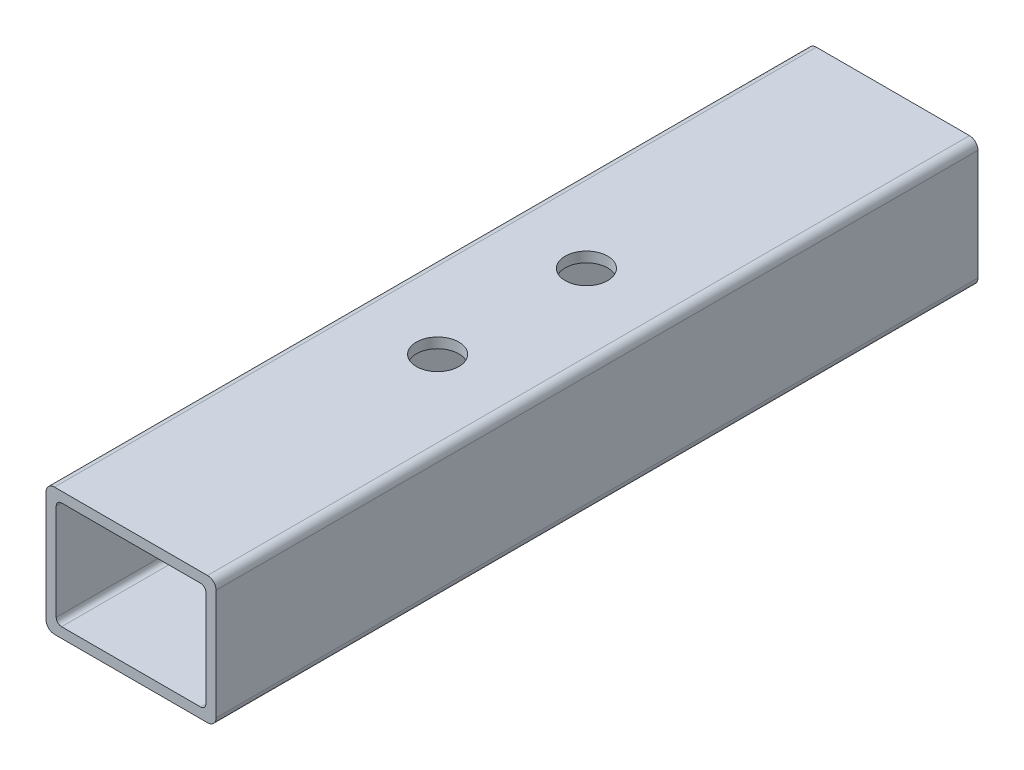
SolidWorks part; units mm, degrees
material "Plain Carbon Steel"
ref_plane "Front" through (0, 0, 0) normal (0, 0, 1) x (1, 0, 0)
ref_plane "Top" through (0, 0, 0) normal (0, 1, 0) x (1, 0, 0)
ref_plane "Right" through (0, 0, 0) normal (1, 0, 0) x (0, 0, -1)
sketch "Sketch1" plane through (0, 0, 0) normal (0, 0, 1) x (1, 0, 0)
  line L0 (-22.352, 0) -> (-25.4, 0) construction
  line L1 (22.86, -19.05) -> (-22.86, -19.05)
  line L2 (25.4, -16.51) -> (25.4, 16.51)
  line L3 (22.86, 19.05) -> (-22.86, 19.05)
  line L4 (-25.4, -16.51) -> (-25.4, 16.51)
  line L5 (25.4, -19.05) -> (-25.4, 19.05) construction
  line L6 (25.4, 19.05) -> (-25.4, -19.05) construction
  line L7 (20.7518, 16.002) -> (-20.7518, 16.002)
  line L8 (22.352, 14.4018) -> (22.352, -14.4018)
  line L9 (20.7518, -16.002) -> (-20.7518, -16.002)
  line L10 (-22.352, 14.4018) -> (-22.352, -14.4018)
  line L11 (22.352, 16.002) -> (-22.352, -16.002) construction
  line L12 (22.352, -16.002) -> (-22.352, 16.002) construction
  line L13 (0, -16.002) -> (0, -19.05) construction
  line L14 (22.352, -14.4018) -> (22.352, -19.05) construction
  line L16 (22.352, -19.05) -> (25.4, -19.05) construction
  arc A0 (-20.7518, -16.002) -> (-22.352, -14.4018) centre (-20.7518, -14.4018) cw
  arc A1 (22.352, -14.4018) -> (20.7518, -16.002) centre (20.7518, -14.4018) cw
  arc A2 (20.7518, 16.002) -> (22.352, 14.4018) centre (20.7518, 14.4018) cw
  arc A3 (-20.7518, 16.002) -> (-22.352, 14.4018) centre (-20.7518, 14.4018) ccw
  arc A4 (22.86, -19.05) -> (25.4, -16.51) centre (22.86, -16.51) ccw
  arc A5 (25.4, 16.51) -> (22.86, 19.05) centre (22.86, 16.51) ccw
  arc A6 (-22.86, 19.05) -> (-25.4, 16.51) centre (-22.86, 16.51) ccw
  arc A7 (-22.86, -19.05) -> (-25.4, -16.51) centre (-22.86, -16.51) cw
  point P0 (0, 0)
  point P6 (0, 0)
  dimension "D2" = 1.6002
  dimension "D3" = 2.54
sketch "Sketch2" plane through (0, 0, 0) normal (1, 0, 0) x (0, 0, -1)
  line L0 (-152.4, 0) -> (152.4, 0) construction
  dimension "Length" = 304.8
ref_plane "Plane1" through (25.4, 0, 0) normal (1, 0, 0) x (0, 0, -1)
sketch "Sketch5" plane through (25.4, 0, 0) normal (1, 0, 0) x (0, 0, -1)
  line L0 (-152.4, 19.05) -> (-152.4, -19.05) construction
  line L1 (152.4, 19.05) -> (152.4, -19.05) construction
sketch "Sketch4" plane through (0, 0, 0) normal (0, 0, 1) x (1, 0, 0)
  line L0 (25.4, -16.51) -> (25.4, 16.51) construction
  line L1 (22.86, 19.05) -> (-22.86, 19.05) construction
  line L2 (-25.4, -16.51) -> (-25.4, 16.51) construction
  line L3 (22.86, -19.05) -> (-22.86, -19.05) construction
  line L4 (22.352, 14.4018) -> (22.352, -14.4018) construction
  line L5 (20.7518, -16.002) -> (-20.7518, -16.002) construction
  line L6 (-22.352, 14.4018) -> (-22.352, -14.4018) construction
  line L7 (20.7518, 16.002) -> (-20.7518, 16.002) construction
  line L8 (25.4, -16.51) -> (25.4, 16.51)
  line L9 (22.86, 19.05) -> (-22.86, 19.05)
  line L10 (-25.4, -16.51) -> (-25.4, 16.51)
  line L11 (22.86, -19.05) -> (-22.86, -19.05)
  line L12 (22.352, 14.4018) -> (22.352, -14.4018)
  line L13 (20.7518, -16.002) -> (-20.7518, -16.002)
  line L14 (-22.352, 14.4018) -> (-22.352, -14.4018)
  line L15 (20.7518, 16.002) -> (-20.7518, 16.002)
  arc A0 (25.4, 16.51) -> (22.86, 19.05) centre (22.86, 16.51) ccw construction
  arc A1 (-22.86, 19.05) -> (-25.4, 16.51) centre (-22.86, 16.51) ccw construction
  arc A2 (-25.4, -16.51) -> (-22.86, -19.05) centre (-22.86, -16.51) ccw construction
  arc A3 (22.86, -19.05) -> (25.4, -16.51) centre (22.86, -16.51) ccw construction
  arc A4 (20.7518, -16.002) -> (22.352, -14.4018) centre (20.7518, -14.4018) ccw construction
  arc A5 (-22.352, -14.4018) -> (-20.7518, -16.002) centre (-20.7518, -14.4018) ccw construction
  arc A6 (-20.7518, 16.002) -> (-22.352, 14.4018) centre (-20.7518, 14.4018) ccw construction
  arc A7 (22.352, 14.4018) -> (20.7518, 16.002) centre (20.7518, 14.4018) ccw construction
  arc A8 (25.4, 16.51) -> (22.86, 19.05) centre (22.86, 16.51) ccw
  arc A9 (-22.86, 19.05) -> (-25.4, 16.51) centre (-22.86, 16.51) ccw
  arc A10 (-25.4, -16.51) -> (-22.86, -19.05) centre (-22.86, -16.51) ccw
  arc A11 (22.86, -19.05) -> (25.4, -16.51) centre (22.86, -16.51) ccw
  arc A12 (20.7518, -16.002) -> (22.352, -14.4018) centre (20.7518, -14.4018) ccw
  arc A13 (-22.352, -14.4018) -> (-20.7518, -16.002) centre (-20.7518, -14.4018) ccw
  arc A14 (-20.7518, 16.002) -> (-22.352, 14.4018) centre (-20.7518, 14.4018) ccw
  arc A15 (22.352, 14.4018) -> (20.7518, 16.002) centre (20.7518, 14.4018) ccw
extrude "Boss-Extrude1" add sketch "Sketch4" along normal blind 227.5637
sketch "Sketch6" plane through (0, 19.05, 0) normal (0, 1, 0) x (1, 0, 0)
  line L0 (0, -227.5637) -> (0, -183.6318) construction
  line L2 (-22.86, -183.6318) -> (22.86, -183.6318) construction
  line L3 (-22.86, 0) -> (-22.86, -227.5637) construction
  line L4 (22.86, 0) -> (22.86, -227.5637) construction
  line L5 (-22.86, -43.9318) -> (22.86, -43.9318) construction
  line L6 (22.86, -227.5637) -> (-22.86, -227.5637) construction
  line L7 (0, -183.6318) -> (0, -43.9318) construction
  line L8 (0, -43.9318) -> (0, 0) construction
  line L9 (22.86, 0) -> (-22.86, 0) construction
  dimension "D1" = 139.7
sketch "Sketch9" plane through (0, 19.05, 0) normal (0, 1, 0) x (1, 0, 0)
  line L0 (0, -227.5637) -> (0, -136.0068) construction
  line L1 (22.86, -227.5637) -> (-22.86, -227.5637) construction
  line L2 (0, -136.0068) -> (0, -91.5568) construction
  line L3 (0, -91.5568) -> (0, 0) construction
  circle A0 centre (0, -136.0068) radius 6.35
  circle A1 centre (0, -91.5568) radius 6.35
  dimension "D2" = 12.7
  dimension "D1" = 44.45
extrude "Cut-Extrude2" cut sketch "Sketch9" along direction (0, -1, 0) on the side against the normal up to next (3.048 mm away)
equation "\"D3@Sketch1\"=\"Outside Width@Sketch1\"*.05"
equation "\"D2@Sketch1\"=\"D1@Sketch1\"*.05"
